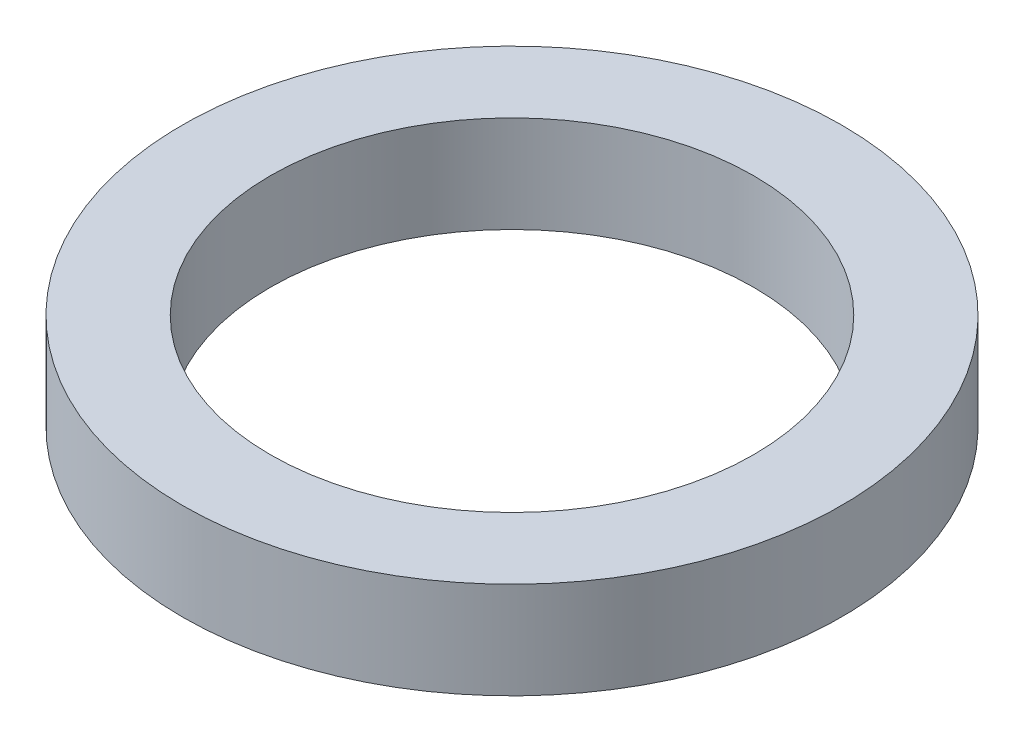
SolidWorks part; units mm, degrees
ref_plane "Front Plane" through (0, 0, 0) normal (0, 0, 1) x (1, 0, 0)
ref_plane "Top Plane" through (0, 0, 0) normal (0, 1, 0) x (1, 0, 0)
ref_plane "Right Plane" through (0, 0, 0) normal (1, 0, 0) x (0, 0, -1)
sketch "Sketch1" plane through (0, 0, 0) normal (0, 1, 0) x (1, 0, 0)
  circle A0 centre (0, 0) radius 37.5
  dimension "FLANGE_OD" = 75
extrude "Boss-Extrude1" add sketch "Sketch1" along normal blind 11
sketch "Sketch2" plane through (0, 0, 0) normal (0, 1, 0) x (1, 0, 0)
  circle A0 centre (0, 0) radius 27.5
  dimension "BORE_D" = 55
extrude "Cut-Extrude1" cut sketch "Sketch2" along normal through all
sketch "Sketch3" plane through (0, 11, 0) normal (0, 1, 0) x (1, 0, 0)
  circle A0 centre (0, 0) radius 17.0953 construction
  circle A1 centre (-17.0953, 0) radius 1.508
  dimension "BOLT_D" = 3.0161
  dimension "BOLT_PCD" = 34.1905
extrude "Cut-Extrude2" cut sketch "Sketch3" against normal blind 8.4171 rebuild error yes
pattern_circular "CirPattern1" count 5 over 360 rebuild error yes
